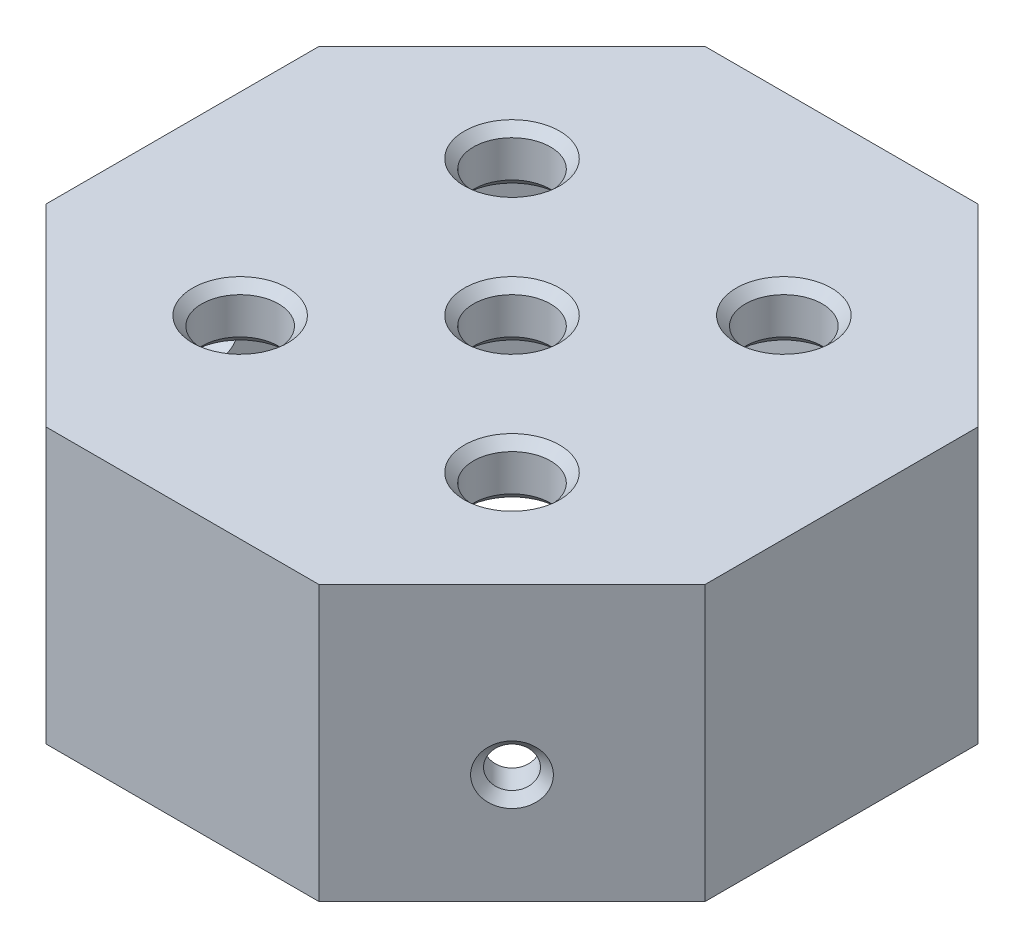
SolidWorks part; units mm, degrees
ref_plane "Спереди" through (0, 0, 0) normal (0, 0, 1) x (1, 0, 0)
ref_plane "Сверху" through (0, 0, 0) normal (0, 1, 0) x (1, 0, 0)
ref_plane "Справа" through (0, 0, 0) normal (1, 0, 0) x (0, 0, -1)
sketch "Эскиз1" plane through (0, 0, 0) normal (0, 1, 0) x (1, 0, 0)
  line L0 (0, 0) -> (0, 18) construction
  line L1 (-6.6274, 16) -> (-16, 6.6274)
  line L2 (-16, 6.6274) -> (-16, -6.6274)
  line L3 (-16, -6.6274) -> (-6.6274, -16)
  line L4 (-6.6274, -16) -> (6.6274, -16)
  line L5 (6.6274, -16) -> (16, -6.6274)
  line L6 (16, -6.6274) -> (16, 6.6274)
  line L7 (16, 6.6274) -> (6.6274, 16)
  line L8 (6.6274, 16) -> (-6.6274, 16)
  line L10 (-7.4558, 18) -> (-18, 7.4558)
  line L11 (-18, 7.4558) -> (-18, -7.4558)
  line L12 (-18, -7.4558) -> (-7.4558, -18)
  line L13 (-7.4558, -18) -> (7.4558, -18)
  line L14 (7.4558, -18) -> (18, -7.4558)
  line L15 (18, -7.4558) -> (18, 7.4558)
  line L16 (18, 7.4558) -> (7.4558, 18)
  line L17 (7.4558, 18) -> (-7.4558, 18)
  circle A0 centre (0, 0) radius 16 construction
  circle A1 centre (0, 0) radius 18 construction
  dimension "D1" = 32
  dimension "D2" = 2
extrude "Бобышка-Вытянуть1" add sketch "Эскиз1" along normal blind 12
sketch "Эскиз2" plane through (0, 12, 0) normal (0, 1, 0) x (1, 0, 0)
  line L8 (7.4558, 18) -> (-7.4558, 18)
  line L9 (-7.4558, 18) -> (-18, 7.4558)
  line L10 (-18, 7.4558) -> (-18, -7.4558)
  line L11 (-18, -7.4558) -> (-7.4558, -18)
  line L12 (-7.4558, -18) -> (7.4558, -18)
  line L13 (7.4558, -18) -> (18, -7.4558)
  line L14 (18, -7.4558) -> (18, 7.4558)
  line L15 (18, 7.4558) -> (7.4558, 18)
  line L16 (7.4558, 18) -> (-7.4558, 18)
  line L17 (-7.4558, 18) -> (-18, 7.4558)
  line L18 (-18, 7.4558) -> (-18, -7.4558)
  line L19 (-18, -7.4558) -> (-7.4558, -18)
  line L20 (-7.4558, -18) -> (7.4558, -18)
  line L21 (7.4558, -18) -> (18, -7.4558)
  line L22 (18, -7.4558) -> (18, 7.4558)
  line L23 (18, 7.4558) -> (7.4558, 18)
  dimension "D1" = 0
extrude "Бобышка-Вытянуть2" add sketch "Эскиз2" along normal blind 3
chamfer "Фаска1" distance 1 angle 45 8 edges at (-11.3137, 12, -11.3137) (-16, 12, 0) (-11.3137, 12, 11.3137) (0, 12, 16) (11.3137, 12, 11.3137) (16, 12, 0) (11.3137, 12, -11.3137) (0, 12, -16)
chamfer "Фаска2" distance 1 angle 45 8 edges at (-16, 0, 0) (-11.3137, 0, -11.3137) (0, 0, -16) (11.3137, 0, -11.3137) (16, 0, 0) (11.3137, 0, 11.3137) (0, 0, 16) (-11.3137, 0, 11.3137)
sketch "Эскиз3" plane through (0, 15, 0) normal (0, 1, 0) x (1, 0, 0)
  line L0 (0, -18) -> (0, 18) construction
  line L2 (-7.425, 7.425) -> (7.425, 7.425) construction
  line L3 (-7.425, 7.425) -> (-7.425, -7.425) construction
  line L4 (-7.425, -7.425) -> (7.425, -7.425) construction
  line L5 (-7.4558, -18) -> (7.4558, -18) construction
  line L6 (7.4558, 18) -> (-7.4558, 18) construction
  line L7 (7.425, 7.425) -> (7.425, -7.425) construction
  line L8 (-7.425, 7.425) -> (7.425, -7.425) construction
  line L9 (-7.425, -7.425) -> (7.425, 7.425) construction
  circle A0 centre (0, 0) radius 2.1
  circle A1 centre (-7.425, 7.425) radius 2.1
  circle A2 centre (7.425, 7.425) radius 2.1
  circle A3 centre (7.425, -7.425) radius 2.1
  circle A4 centre (-7.425, -7.425) radius 2.1
  point P8 (0, 0)
  dimension "D1" = 4.2
  dimension "D2" = 14.85
  dimension "D3" = 14.85
extrude "Вырез-Вытянуть1" cut sketch "Эскиз3" against normal through all
chamfer "Фаска3" distance 0.5 angle 45 5 edges at (0, 12, 2.1) (-7.425, 12, -5.325) (-7.425, 12, 9.525) (7.425, 12, 9.525) (7.425, 12, -5.325)
sketch "Эскиз4" plane through (-12.7279, 0, 12.7279) normal (-0.7071, 0, 0.7071) x (0.7071, 0, 0.7071)
  line L0 (0, 15) -> (0, 0) construction
  line L1 (-7.4558, 15) -> (7.4558, 15) construction
  line L2 (-7.4558, 0) -> (7.4558, 0) construction
  circle A0 centre (0, 6) radius 1.1
  point P8 (0, 7.5)
  dimension "D2" = 2.2
  dimension "D3" = 9
  dimension "D1" = 1.5
extrude "Вырез-Вытянуть2" cut sketch "Эскиз4" against normal through all
sketch "Эскиз5" plane through (12.7279, 0, 12.7279) normal (0.7071, 0, 0.7071) x (0.7071, 0, -0.7071)
  line L0 (0, 15) -> (0, 0) construction
  line L1 (-7.4558, 15) -> (7.4558, 15) construction
  line L2 (-7.4558, 0) -> (7.4558, 0) construction
  circle A0 centre (0, 6) radius 1.1
  dimension "D1" = 9
  dimension "D2" = 2.2
extrude "Вырез-Вытянуть3" cut sketch "Эскиз5" against normal through all
sketch "Эскиз6" plane through (-18, 0, 0) normal (-1, 0, 0) x (0, 0, 1)
  line L0 (0, 15) -> (0, 0) construction
  line L1 (-7.4558, 15) -> (7.4558, 15) construction
  line L2 (-7.4558, 0) -> (7.4558, 0) construction
  circle A0 centre (0, 6) radius 1.1
  dimension "D1" = 9
  dimension "D2" = 2.2
extrude "Вырез-Вытянуть4" cut sketch "Эскиз6" against normal up to surface (2 mm away) up to face at (-16, 6, 0)
chamfer "Фаска4" distance 0.5 angle 45 5 edges at (-11.9501, 6, 13.5057) (-18, 6, 1.1) (-11.9501, 6, -13.5057) (13.5057, 6, 11.9501) (13.5057, 6, -11.9501)
chamfer "Фаска5" distance 0.5 angle 45 5 edges at (-7.425, 15, -5.325) (7.425, 15, -5.325) (0, 15, 2.1) (7.425, 15, 9.525) (-7.425, 15, 9.525)
